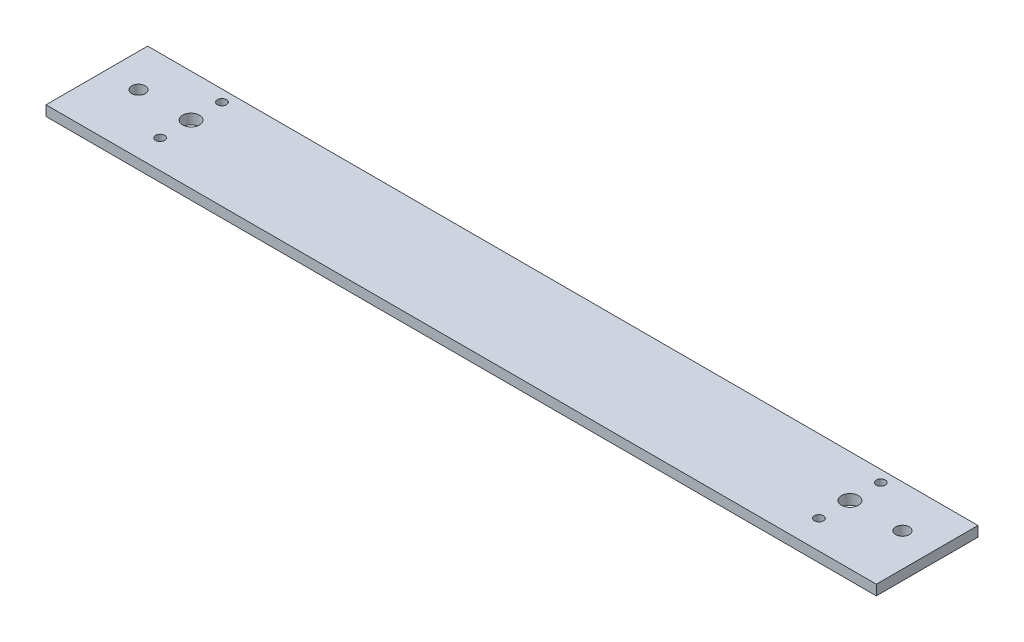
SolidWorks part; units mm, degrees
material "Maple"
ref_plane "Front Plane" through (0, 0, 0) normal (0, 0, 1) x (1, 0, 0)
ref_plane "Top Plane" through (0, 0, 0) normal (0, 1, 0) x (1, 0, 0)
ref_plane "Right Plane" through (0, 0, 0) normal (1, 0, 0) x (0, 0, -1)
sketch "Sketch2" plane through (0, 0, 0) normal (0, 1, 0) x (1, 0, 0)
  line L1 (-245, 30) -> (245, 30)
  line L2 (-245, 30) -> (-245, -30)
  line L3 (-245, -30) -> (245, -30)
  line L4 (245, 30) -> (245, -30)
  line L5 (-245, 30) -> (245, -30) construction
  line L6 (-245, -30) -> (245, 30) construction
  point P0 (0, 0)
  dimension "D1" = 490
  dimension "D2" = 60
extrude "Boss-Extrude1" add sketch "Sketch2" along normal blind 6
ref_plane "Plane1" through (0, 3, 0) normal (0, 1, 0) x (1, 0, 0)
hole_wizard "Ø10.0 (10) Diameter Hole1" positions "Sketch4" profile "Sketch3" hole size "Ø10.0" standard "ANSI Metric" end condition through all
sketch "Sketch4" plane through (0, 6, 0) normal (0, 1, 0) x (1, 0, 0)
  circle A0 centre (194.4, 5) radius 4 construction
  point P0 (194.4, 5)
sketch "Sketch3" plane through (194.4, 6, -5) normal (1, 0, 0) x (0, 0, 1)
  line L0 (0, 0) -> (0, 6)
  line L1 (0, 6) -> (5, 6)
  line L2 (5, 6) -> (5, 0)
  line L5 (5, 0) -> (0, 0)
  line L11 (0, -6.35) -> (0, 107.95) construction
  dimension "Thru Hole Dia." = 10
  dimension "Thru Hole Depth" = 6
hole_wizard "M5 Clearance Hole1" positions "Sketch6" profile "Sketch5" hole size "M5" standard "ANSI Metric" end condition through all
sketch "Sketch6" plane through (0, 6, 0) normal (0, 1, 0) x (1, 0, 0)
  circle A0 centre (194.4, 23.25) radius 2.65 construction
  circle A1 centre (194.4, -13.25) radius 2.65 construction
  point P0 (194.4, -13.25)
  point P2 (194.4, 23.25)
sketch "Sketch5" plane through (194.4, 6, 13.25) normal (1, 0, 0) x (0, 0, 1)
  line L0 (0, 0) -> (0, 6)
  line L1 (0, 6) -> (2.65, 6)
  line L2 (2.65, 6) -> (2.65, 0)
  line L5 (2.65, 0) -> (0, 0)
  line L11 (0, -6.35) -> (0, 107.95) construction
  dimension "Thru Hole Dia." = 5.3
  dimension "Thru Hole Depth" = 6
hole_wizard "Ø8.0 (8) Diameter Hole1" positions "Sketch8" profile "Sketch7" hole size "Ø8.0" standard "ANSI Metric" end condition through all
sketch "Sketch8" plane through (0, 6, 0) normal (0, 1, 0) x (1, 0, 0)
  point P0 (225.4, 5)
sketch "Sketch7" plane through (225.4, 6, -5) normal (1, 0, 0) x (0, 0, 1)
  line L0 (0, 0) -> (0, 6)
  line L1 (0, 6) -> (4, 6)
  line L2 (4, 6) -> (4, 0)
  line L5 (4, 0) -> (0, 0)
  line L11 (0, -6.35) -> (0, 107.95) construction
  dimension "Thru Hole Dia." = 8
  dimension "Thru Hole Depth" = 6
mirror "Mirror1" about plane through (0, 0, 0) normal (1, 0, 0) of "Ø8.0 (8) Diameter Hole1", "Ø10.0 (10) Diameter Hole1", "M5 Clearance Hole1"
